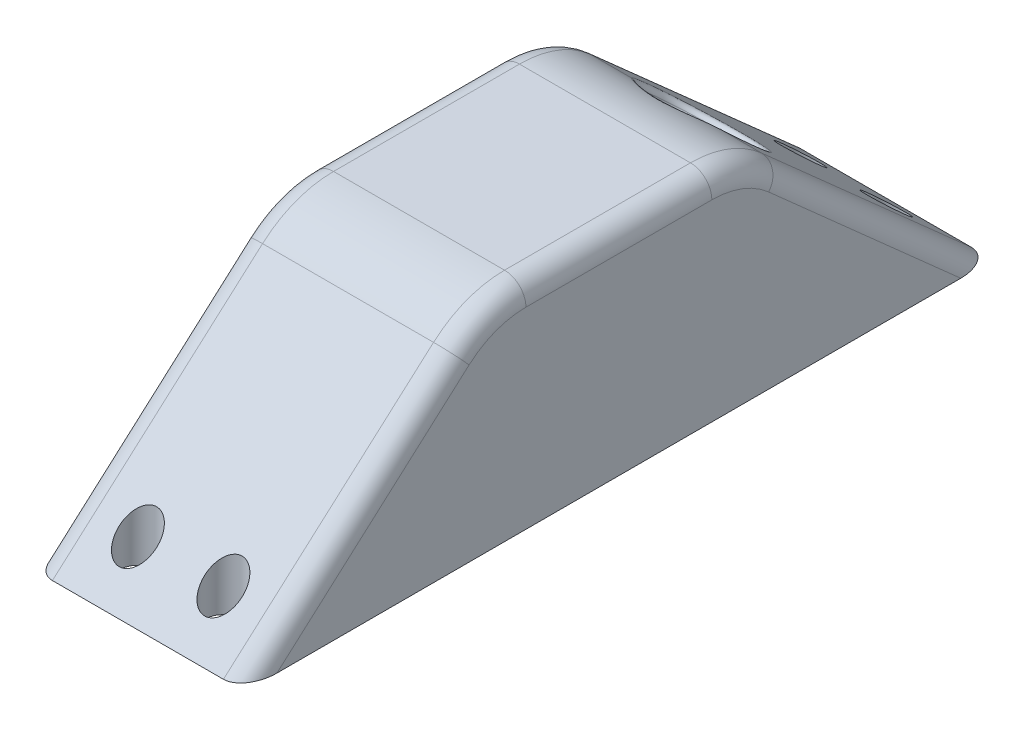
SolidWorks part; units mm, degrees
ref_plane "Front Plane" through (0, 0, 0) normal (0, 0, 1) x (1, 0, 0)
ref_plane "Top Plane" through (0, 0, 0) normal (0, 1, 0) x (1, 0, 0)
ref_plane "Right Plane" through (0, 0, 0) normal (1, 0, 0) x (0, 0, -1)
sketch "Sketch1" plane through (0, 0, 0) normal (0, 1, 0) x (1, 0, 0)
  line L0 (-14.05, 27.5) -> (14.05, 27.5)
  line L1 (-14.05, 27.5) -> (-14.05, -27.5)
  line L2 (14.05, 27.5) -> (14.05, -27.5)
  line L3 (-14.05, -27.5) -> (14.05, -27.5)
  line L4 (-14.05, 27.5) -> (14.05, -27.5) construction
  line L5 (14.05, 27.5) -> (-14.05, -27.5) construction
  point P1 (0, 0)
  dimension "D1" = 28.1
  dimension "D2" = 55
ref_plane "Plane1" through (0, 20, 0) normal (0, 1, 0) x (1, 0, 0)
sketch "Sketch2" plane through (0, 0, 0) normal (1, 0, 0) x (0, 0, -1)
  line L0 (-35, 0) -> (35, 0)
  line L1 (0, 0) -> (0, 20) construction
  line L2 (15.455, 20) -> (-15.455, 20) construction
  line L3 (-8.698, 20) -> (8.698, 20)
  line L4 (-35, 0) -> (-15.3416, 17.4741)
  line L5 (15.3416, 17.4741) -> (35, 0)
  arc A0 (8.698, 20) -> (15.3416, 17.4741) centre (8.698, 10) cw
  arc A1 (-8.698, 20) -> (-15.3416, 17.4741) centre (-8.698, 10) ccw
  point P4 (0, 0)
  point P12 (0, 20)
  point P14 (12.5, 20)
  point P17 (-12.5, 20)
  dimension "D3" = 10
  dimension "D1" = 70
  dimension "D2" = 25
extrude "Boss-Extrude1" add sketch "Sketch2" along normal blind 20
fillet "Fillet1" radius 2 10 edges at (20, 8.737, -25.1708) (20, 19.3472, -12.2518) (20, 8.737, 25.1708) (20, 19.3472, 12.2518) (20, 20, 0) (0, 8.737, -25.1708) (0, 19.3472, -12.2518) (0, 20, 0) (0, 19.3472, 12.2518) (0, 8.737, 25.1708)
ref_plane "Plane2" through (0, -17.3793, -19.5517) normal (0, -0.6644, -0.7474) x (-1, 0, 0)
sketch "Sketch3" plane through (0, -17.3793, -19.5517) normal (0, -0.6644, -0.7474) x (-1, 0, 0)
  line L0 (-18, 23.2527) -> (-2, 23.2527) construction
  line L1 (-17.05, 10.2527) -> (-2.95, 10.2527)
  line L2 (-17.05, 10.2527) -> (-17.05, -9.2473)
  line L3 (-17.05, -9.2473) -> (-2.95, -9.2473)
  line L4 (-2.95, 10.2527) -> (-2.95, -9.2473)
  line L5 (-20, -21.2527) -> (-20, 21.2527) construction
  line L7 (0, -21.2527) -> (0, 21.2527) construction
  dimension "D1" = 2.95
  dimension "D2" = 19.5
  dimension "D3" = 13
  dimension "D4" = 2.95
extrude "Cut-Extrude1" cut sketch "Sketch3" against normal blind 34 contours L2 L1 L4 L3
sketch "Sketch4" plane through (0, 7.663, -6.8115) normal (0, -0.7474, 0.6644) x (1, 0, 0)
  line L0 (2.95, 7.8407) -> (2.95, -11.5343) construction
  line L1 (2.95, 5.4657) -> (17.05, 5.4657)
  line L2 (2.95, 5.4657) -> (2.95, -11.5343)
  line L3 (2.95, -11.5343) -> (17.05, -11.5343)
  line L4 (17.05, 5.4657) -> (17.05, -11.5343)
  line L5 (17.05, 7.8407) -> (17.05, -11.5343) construction
  line L7 (10, 5.4657) -> (10, -11.5343) construction
  line L8 (2.95, -3.0343) -> (17.05, -3.0343) construction
  line L9 (2.95, -11.5343) -> (17.05, -11.5343) construction
  line L10 (2.95, -9.5343) -> (17.05, -9.5343)
  line L11 (2.95, -9.5343) -> (2.95, 3.4657)
  line L12 (2.95, 3.4657) -> (17.05, 3.4657)
  line L13 (17.05, -9.5343) -> (17.05, 3.4657)
  line L14 (2.95, -9.5343) -> (17.05, 3.4657) construction
  line L15 (2.95, 3.4657) -> (17.05, -9.5343) construction
  line L16 (4.05, -8.9343) -> (15.95, -8.9343)
  line L17 (4.05, -8.9343) -> (4.05, 2.8657)
  line L18 (4.05, 2.8657) -> (15.95, 2.8657)
  line L19 (15.95, -8.9343) -> (15.95, 2.8657)
  line L20 (4.05, -8.9343) -> (15.95, 2.8657) construction
  line L21 (4.05, 2.8657) -> (15.95, -8.9343) construction
  circle A0 centre (10, -3.0343) radius 4.75
  point P14 (10, -3.0343)
  point P19 (10, -3.0343)
  dimension "D6" = 9.5
  dimension "D1" = 17
  dimension "D3" = 13
  dimension "D4" = 11.8
  dimension "D5" = 11.9
extrude "Cut-Extrude2" cut sketch "Sketch4" against normal blind 20 contours A0 | A0 region at (10, 5.6471, -9.0794)
extrude "Cut-Extrude3" cut sketch "Sketch4<5>" against normal blind 11 contours L16 L19 L18 L17 A0 region at (4.2176, 5.6471, -9.0794)
sketch "Sketch4<5>" plane through (0, 7.663, -6.8115) normal (0, -0.7474, 0.6644) x (1, 0, 0) same geometry as "Sketch4"
extrude "Cut-Extrude4" cut sketch "Sketch4<6>" against normal blind 5.3 contours L12 L2 L10 L4 L19 L16 L17 L18 region at (10, 9.838, -4.3646)
sketch "Sketch4<6>" plane through (0, 7.663, -6.8115) normal (0, -0.7474, 0.6644) x (1, 0, 0) same geometry as "Sketch4"
extrude "Cut-Extrude5" cut sketch "Sketch4<8>" against normal blind 2 contours L1 L4 L3 L2
sketch "Sketch4<8>" plane through (0, 7.663, -6.8115) normal (0, -0.7474, 0.6644) x (1, 0, 0) same geometry as "Sketch4"
fillet "Fillet2" radius 0.5 2 edges at (10, 12.2077, -21.2664) (10.7874, 18.3901, -14.1392)
ref_plane "Plane3" through (0, 10, 0) normal (0, 1, 0) x (1, 0, 0)
sketch "Sketch7" plane through (0, 10, 0) normal (0, 1, 0) x (1, 0, 0)
  line L0 (18, 35) -> (2, 35) construction
  line L1 (18, 15.3416) -> (18, 35) construction
  line L2 (10, 35) -> (10, -35) construction
  line L3 (18, -35) -> (2, -35) construction
  line L4 (10, 0) -> (20, 0) construction
  line L5 (20, 8.698) -> (20, -8.698) construction
  circle A0 centre (14, 31) radius 1.75
  circle A1 centre (6, 31) radius 1.75
  circle A2 centre (14, -31) radius 1.75
  circle A3 centre (6, -31) radius 1.75
  dimension "D1" = 3.5
  dimension "D2" = 4
  dimension "D3" = 4
extrude "Cut-Extrude7" cut sketch "Sketch7" against normal blind 15
